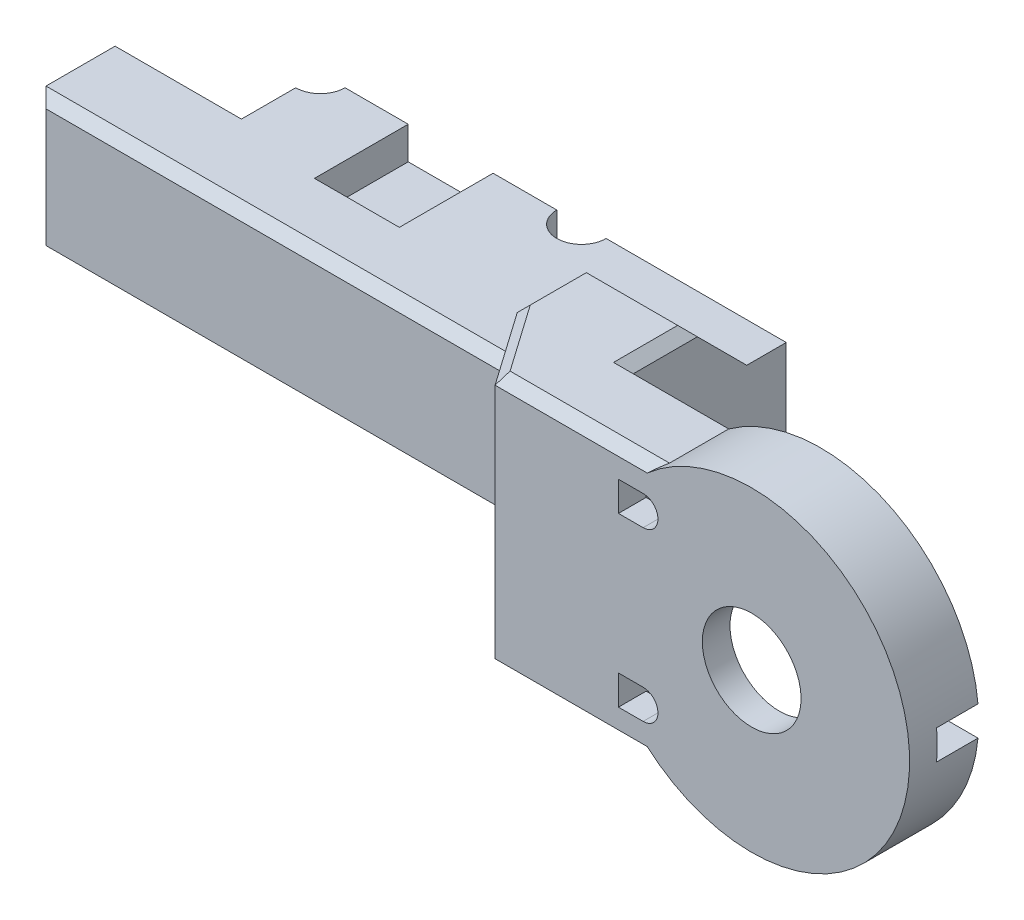
SolidWorks part; units mm, degrees
note: '?' marks a value the reader was unsure of.
ref_plane "Front Plane" through (0, 0, 0) normal (0, 0, 1) x (1, 0, 0)
ref_plane "Top Plane" through (0, 0, 0) normal (0, 1, 0) x (1, 0, 0)
ref_plane "Right Plane" through (0, 0, 0) normal (1, 0, 0) x (0, 0, -1)
sketch "Sketch1" plane through (0, 0, 0) normal (0, 0, 1) x (1, 0, 0)
  line L0 (-1000, 0) -> (49000, 0) construction
  line L1 (-1003.2111, 6.5) -> (48996.7889, 6.5) construction
  line L2 (-1004.8419, -6.5) -> (48995.1581, -6.5) construction
  line L3 (-13, -6.5) -> (-13, 6.5)
  line L4 (-13, 6.5) -> (-4.6637, 6.5)
  line L5 (-13, -6.5) -> (-4.6637, -6.5)
  arc A0 (-4.6637, -6.5) -> (-4.6637, 6.5) centre (0, 0) ccw
  arc A1 (-8, 0) -> (-4.6637, -6.5) centre (0, 0) ccw construction
  arc A2 (-4.6637, 6.5) -> (-8, 0) centre (0, 0) ccw construction
  point P12 (-13, 0)
  dimension "D1" = 16
  dimension "D2" = 13
  dimension "D3" = 13
extrude "Boss-Extrude1" add sketch "Sketch1" along normal blind 3.5
sketch "Sketch2" plane through (0, 0, 0) normal (0, 0, -1) x (-1, 0, 0)
  line L0 (-1000, 0) -> (49000, 0) construction
  line L1 (0, -1000) -> (0, 49000) construction
  line L3 (-5.75, -1008.4841) -> (-5.75, -0.75) construction
  line L4 (-998.5902, -5.75) -> (49001.4098, -5.75) construction
  line L5 (-997.2865, 5.75) -> (49002.7135, 5.75) construction
  line L6 (-5.75, -0.75) -> (-7.9648, -0.75)
  line L7 (-5.75, 0.75) -> (-7.9648, 0.75)
  line L8 (-5.75, -2.5) -> (-5.75, -0.75)
  line L9 (-5.75, -2.5) -> (-2.5, -5.75)
  line L10 (-5.75, 2.5) -> (-2.5, 5.75)
  line L11 (-2.5, -5.75) -> (6.75, -5.75)
  line L12 (-2.5, 5.75) -> (6.75, 5.75)
  line L13 (6.75, -1004.2518) -> (6.75, 48995.7482) construction
  line L15 (6.75, -5.75) -> (6.75, 5.75)
  line L16 (-5.75, 0) -> (-5.75, 0.75) construction
  line L17 (-5.75, 0.75) -> (-5.75, 2.5)
  line L18 (-5.75, 0) -> (-5.75, 0.75) construction
  line L19 (-5.75, 0.75) -> (-5.75, 48991.5159) construction
  line L20 (-5.75, -0.75) -> (-5.75, 0) construction
  line L21 (-5.75, -0.75) -> (-5.75, 0) construction
  line L22 (-2.5, -1002.5522) -> (-2.5, 48997.4478) construction
  arc A0 (-7.9648, -0.75) -> (-7.9648, 0.75) centre (0, 0) cw
  circle A1 centre (0, 0) radius 8 construction
  point P25 (-5.5, 0)
  dimension "D6" = 8
  dimension "D1" = 5.75
  dimension "D2" = 5.75
  dimension "D3" = 5.75
  dimension "D4" = 0.75
  dimension "D5" = 0.75
  dimension "D7" = 5
  dimension "D8" = 45
  dimension "D9" = 45
  dimension "D10" = 2.5
  dimension "D11" = 6.75
extrude "Cut-Extrude1" cut sketch "Sketch2" against normal blind 2.1
sketch "Sketch3" plane through (0, 0, 2.1) normal (0, 0, -1) x (-1, 0, 0)
  line L0 (5.5, -5) -> (6.75, -5)
  line L1 (5.5, -3.5) -> (6.75, -3.5)
  line L2 (5.5, 3.5) -> (6.75, 3.5)
  line L3 (5.5, 5) -> (6.75, 5)
  line L5 (6.75, -5.75) -> (6.75, 5.75) construction
  line L7 (6.75, 5) -> (6.75, 3.5)
  line L9 (6.75, -3.5) -> (6.75, -5)
  circle A0 centre (0, 0) radius 2.5
  arc A1 (5.5, -3.5) -> (5.5, -5) centre (5.5, -4.25) ccw
  arc A2 (5.5, 5) -> (5.5, 3.5) centre (5.5, 4.25) ccw
  arc A6 (5.5, -5) -> (5.5, -3.5) centre (5.5, -4.25) ccw construction
  arc A7 (5.5, 3.5) -> (5.5, 5) centre (5.5, 4.25) ccw construction
  point P4 (0, 0)
  dimension "D1" = 5
  dimension "D2" = 1.5
  dimension "D3" = 1.5
extrude "Cut-Extrude2" cut sketch "Sketch3" against normal through all
sketch "Sketch5" plane through (0, 0, 3.5) normal (0, 0, -1) x (-1, 0, 0)
  line L0 (201000, 0) -> (-249000, 0) construction
  line L1 (13, -6.5) -> (10, -6.5)
  line L2 (13, -6.5) -> (13, 6.5)
  line L3 (13, 6.5) -> (10, 6.5)
  line L4 (10, -6.5) -> (10, 6.5)
  line L7 (13, 6.5) -> (13, -6.5) construction
  dimension "D1" = 10
  dimension "D2" = 6.5
  dimension "D3" = 6.5
extrude "Boss-Extrude3" add sketch "Sketch5" along normal blind 11.75
ref_plane "Plane1" through (-40, 0, 0) normal (1, 0, 0) x (0, 0, -1)
sketch "Sketch6" plane through (-13, 0, 0) normal (-1, 0, 0) x (0, 0, 1)
  line L0 (-8.25, 6.5) -> (3.5, 6.5) construction
  line L1 (-8.25, 6.5) -> (3.5, 6.5)
  line L2 (-8.25, 6.5) -> (-8.25, -6.5)
  line L3 (-8.25, -6.5) -> (3.5, -6.5)
  line L4 (3.5, 6.5) -> (3.5, -6.5)
  line L5 (3.5, 6.5) -> (3.5, -6.5) construction
extrude "Boss-Extrude4" add sketch "Sketch6" along normal up to surface (27 mm away) up to plane "Plane1"
sketch "Sketch7" plane through (0, 0, -8.25) normal (0, 0, -1) x (-1, 0, 0)
  line L0 (10, -6.5) -> (40, -6.5) construction
  line L1 (40, 6.5) -> (31.1, 6.5)
  line L2 (40, 6.5) -> (40, -6.5)
  line L3 (40, -6.5) -> (31.1, -6.5)
  line L4 (31.1, 6.5) -> (31.1, -6.5)
  dimension "D1" = 8.9
extrude "Cut-Extrude3" cut sketch "Sketch7" against normal blind 4
sketch "Sketch26" plane through (0, 6.5, 0) normal (0, 1, 0) x (1, 0, 0)
  line L0 (-40, -6.4625) -> (-40, 6.4625) construction
  line L1 (-13, -3.5) -> (-40, -3.5)
  line L2 (-13, -3.5) -> (-13, 0.25)
  line L3 (-13, 0.25) -> (-40, 0.25)
  line L4 (-40, -3.5) -> (-40, 0.25)
  line L5 (-40, 4.25) -> (-31.1, 4.25) construction
  line L6 (-4.6637, -3.5) -> (-40, -3.5) construction
  dimension "D1" = 4
extrude "Cut-Extrude15" cut sketch "Sketch26" against normal through all both and the other way through all
chamfer "Chamfer1" distance 3.75 angle 35 1 edges at (-13, 0, -0.25)
sketch "Sketch19" plane through (-6.75, 0, 0) normal (1, 0, 0) x (0, 0, -1)
  line L1 (-2.1, 4) -> (0.25, 4)
  line L2 (-2.1, 4) -> (-2.1, -4)
  line L3 (-2.1, -4) -> (0.25, -4)
  line L4 (0.25, 4) -> (0.25, -4)
  line L9 (-2.1, -3.5) -> (-2.1, 3.5) construction
  point P4 (0.25, 0)
  dimension "D1" = 2.35
  dimension "D2" = 8
ref_plane "Plane3" through (-15.6258, 0, 0) normal (1, 0, 0) x (0, 0, -1)
sketch "Sketch29" plane through (-15.6258, 0, 0) normal (1, 0, 0) x (0, 0, -1)
  line L1 (0.25, 3.5) -> (-1.95, 3.5)
  line L2 (0.25, 3.5) -> (0.25, -3.5)
  line L3 (0.25, -3.5) -> (-1.95, -3.5)
  line L4 (-1.95, 3.5) -> (-1.95, -3.5)
  line L6 (0.25, 4) -> (0.25, -4) construction
  point P7 (0.25, 0)
  dimension "D1" = 7
  dimension "D2" = 2.2
loft "Cut-Loft1" cut profiles "Sketch19", "Sketch29"
sketch "Sketch28" plane through (0, 6.5, 0) normal (0, 1, 0) x (1, 0, 0)
  line L1 (-10, 8.25) -> (-40, 8.25)
  line L2 (-10, 8.25) -> (-10, 0.25)
  line L3 (-10, 0.25) -> (-40, 0.25)
  line L4 (-40, 8.25) -> (-40, 0.25)
  line L7 (-40, -6.4625) -> (-40, 6.4625) construction
  line L9 (-15.6258, 0.25) -> (-10, 0.25)
  line L10 (-15.6258, 0.25) -> (-15.6258, 3.25)
  line L11 (-15.6258, 3.25) -> (-10, 3.25)
  line L12 (-10, 0.25) -> (-10, 3.25)
  dimension "D1" = 3
extrude "Cut-Extrude16" cut sketch "Sketch28" against normal blind 3
sketch "Sketch30" plane through (0, -6.5, 0) normal (0, -1, 0) x (1, 0, 0)
  line L0 (-15.6258, -4.5375) -> (-15.6258, 4.5375) construction
  line L1 (-10, -0.25) -> (-40, -0.25)
  line L2 (-10, -0.25) -> (-10, -8.25)
  line L3 (-10, -8.25) -> (-40, -8.25)
  line L4 (-40, -0.25) -> (-40, -8.25)
  line L5 (-10, -0.25) -> (-15.6258, -0.25)
  line L6 (-10, -0.25) -> (-10, -3.25)
  line L7 (-10, -3.25) -> (-15.6258, -3.25)
  line L8 (-15.6258, -0.25) -> (-15.6258, -3.25)
  line M8 (-15.6258, -0.25) -> (-40, -0.25)
  line M9 (-40, -0.25) -> (-40, -4.25)
  line M10 (-40, -4.25) -> (-31.1, -4.25)
  line M11 (-31.1, -4.25) -> (-31.1, -8.25)
  line M12 (-31.1, -8.25) -> (-10, -8.25)
  line M13 (-10, -8.25) -> (-10, 0)
  dimension "D1" = 3
extrude "Cut-Extrude17" cut sketch "Sketch30" against normal blind 3 contours L8 L7 M8 M9 M10 M11 M12 M13
chamfer "Chamfer3" distance 3 angle 45 2 edges at (-12.8129, 3.5, -3.25) (-12.8129, -3.5, -3.25)
sketch "Sketch22" plane through (-40, 0, 0) normal (-1, 0, 0) x (0, 0, 1)
  line L0 (-2.125, -3.5) -> (-2.125, 3.5) construction
  line L1 (-0.25, -3.5) -> (-4.25, -3.5) construction
  line L2 (-4.25, 3.5) -> (-0.25, 3.5) construction
  line L3 (-4.25, -3.5) -> (-4.25, 3.5) construction
  arc A0 (-2.125, -1.625) -> (-2.125, -0.475) centre (-2.125, -1.05) ccw
  arc A1 (-2.125, 0.475) -> (-2.125, 1.625) centre (-2.125, 1.05) ccw
  arc A2 (-2.125, -0.475) -> (-2.125, -1.625) centre (-2.125, -1.05) ccw construction
  arc A3 (-2.125, 1.625) -> (-2.125, 0.475) centre (-2.125, 1.05) ccw construction
  ellipse E0 centre (-2.125, -1.05) end of major axis (-2.875, -1.05) minor radius 0.575 (-2.125, -0.475) -> (-2.125, -1.625) ccw
  ellipse E1 centre (-2.125, 1.05) end of major axis (-1.375, 1.05) minor radius 0.575 (-2.125, 1.625) -> (-2.125, 0.475) ccw
  ellipse E2 centre (-2.125, -1.05) end of major axis (-2.875, -1.05) minor radius 0.575 (-2.125, -1.625) -> (-2.125, -0.475) ccw construction
  ellipse E3 centre (-2.125, 1.05) end of major axis (-1.375, 1.05) minor radius 0.575 (-2.125, 0.475) -> (-2.125, 1.625) ccw construction
  point P10 (-2.125, 0)
  dimension "D2" = 1.15
  dimension "D3" = 1.15
  dimension "D1" = 1.05
  dimension "D4" = 2.1
  dimension "D5" = 2.125
  dimension "D6" = 0.75
  dimension "D7" = 0.75
extrude "Cut-Extrude13" cut sketch "Sketch22" against normal through all
fillet "Fillet6" radius 0.25 8 edges at (-40, 1.05, -1.55) (-40, -1.05, -1.55) (-10, 1.05, -1.55) (-10, -1.05, -1.55) (-10, 1.05, -2.875) (-40, 1.05, -2.875) (-10, -1.05, -2.875) (-40, -1.05, -2.875)
chamfer "Chamfer4" distance 0.5 angle 45 11 edges at (-40, 0, -0.25) (-8.8318, -6.5, 3.5) (-14.3129, -6.5, 1.625) (-8.8318, 6.5, 3.5) (-14.3129, 6.5, 1.625) (-10, -6.5, -1.625) (-10, 6.5, -1.625) (-15.6258, -6.5, -1.75) (-15.6258, 6.5, -1.75)
sketch "Sketch31" plane through (0, 3.5, 0) normal (0, 1, 0) x (1, 0, 0)
  line L0 (-10, 8.25) -> (-31.1, 8.25) construction
  line L2 (-31.1, 8.25) -> (-31.1, 4.25) construction
  circle A0 centre (-20.3712, 8.25) radius 1.25
  dimension "D1" = 10.7288
  dimension "D2" = 2.5
extrude "Cut-Extrude18" cut sketch "Sketch31" against normal through all
ref_plane "Plane2" [suppressed] through (0, 0, -8.25) normal (0, 0, 1) x (1, 0, 0)
sketch "Sketch25" [suppressed] plane through (0, 0, -8.25) normal (0, 0, 1) x (1, 0, 0)
  line L0 (-18.0119, 6.5) -> (-6.6551, 6.5)
  line L2 (-5.8095, 5.5) -> (-39, 5.5) construction
  line L3 (-15.5693, 3.589) -> (-18.0119, 6.5)
  line L4 (-39, 6.5) -> (-4.6637, 6.5) construction
  line L6 (-40, -5.5) -> (-40, 5.5) construction
  line L7 (-15.5693, 3.589) -> (-14.4585, 4.5211)
  line L8 (-14.4585, 4.5211) -> (-12.2088, 1.8399)
  line L9 (-12.2088, 1.8399) -> (-6.6551, 6.5)
  line L15 (-16.3038, 5.5) -> (-10, 5.5) construction
  line L20 (0, 0) -> (-9.2453, 11.0181) construction
  dimension "D1" = 40
  dimension "D2" = 3.8
  dimension "D3" = 0.92
  dimension "D4" = 1.45
  dimension "D5" = 3.5
ref_axis "Axis1" [suppressed] through (0, 0, -8.25) along (-0.6428, 0.766, 0)?
revolve "Cut-Revolve1" [suppressed] cut sketch "Sketch25" angle 360 about L20
sketch "Sketch32" plane through (0, 3.5, 0) normal (0, 1, 0) x (1, 0, 0)
  line L0 (-32.35, 8.25) -> (-33.6, 8.25) construction
  line L1 (-31.1, 4.25) -> (-33.6, 4.25)
  line L2 (-31.1, 4.25) -> (-31.1, 8.25)
  line L3 (-31.1, 8.25) -> (-32.35, 8.25)
  line L4 (-33.6, 4.25) -> (-33.6, 7)
  line L5 (-33.6, 7) -> (-33.6, 8.25) construction
  arc A0 (-33.6, 7) -> (-32.35, 8.25) centre (-33.6, 8.25) ccw
  arc A1 (-32.35, 8.25) -> (-33.6, 7) centre (-33.6, 8.25) ccw construction
  dimension "D1" = 2.5
extrude "Boss-Extrude5" add sketch "Sketch32" against normal up to surface (7 mm away) up to face at (-23.4194, -3.5, -5.15)
sketch "Sketch33" plane through (0, 3.5, 0) normal (0, 1, 0) x (1, 0, 0)
  line L0 (-27, 8.25) -> (-27, 3.5) construction
  line L1 (-21.6212, 8.25) -> (-32.35, 8.25) construction
  line L2 (-29.15, 3.5) -> (-24.85, 3.5)
  line L3 (-24.85, 3.5) -> (-24.85, 8.25)
  line L4 (-24.85, 8.25) -> (-29.15, 8.25)
  line L5 (-29.15, 8.25) -> (-29.15, 3.5)
  line L6 (-33.6, 7) -> (-33.6, 4.25) construction
  point P6 (-27, 3.5)
  dimension "D1" = 4.75
  dimension "D2" = 4.3
  dimension "D3" = 6.6
extrude "Cut-Extrude19" cut sketch "Sketch33" against normal blind 1.65
